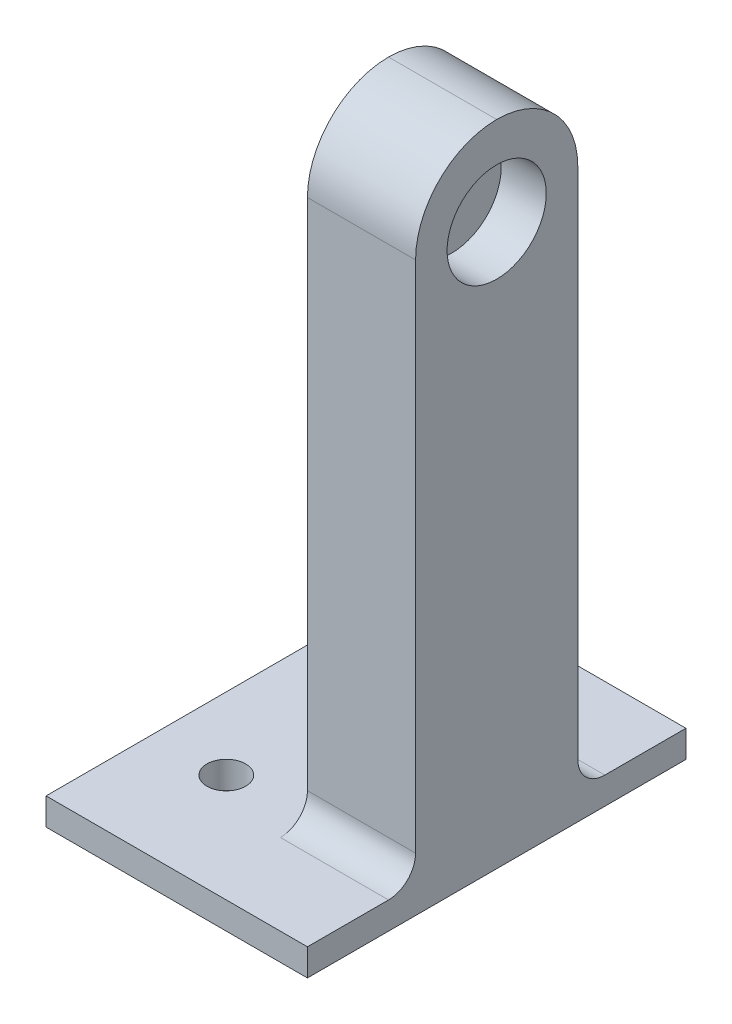
SolidWorks part; units mm, degrees
ref_plane "Front Plane" through (0, 0, 0) normal (0, 0, 1) x (1, 0, 0)
ref_plane "Top Plane" through (0, 0, 0) normal (0, 1, 0) x (1, 0, 0)
ref_plane "Right Plane" through (0, 0, 0) normal (1, 0, 0) x (0, 0, -1)
sketch "Sketch1" plane through (0, 0, 0) normal (0, 1, 0) x (1, 0, 0)
  line L1 (0, 0) -> (94, 0)
  line L2 (0, 0) -> (0, -42)
  line L3 (0, -42) -> (94, -42)
  line L4 (94, 0) -> (94, -42)
  dimension "D1" = 94
  dimension "D2" = 42
extrude "Boss-Extrude1" add sketch "Sketch1" along normal blind 3
sketch "Sketch2" plane through (0, 0, 0) normal (0, -1, 0) x (1, 0, 0)
  line L0 (94, 0) -> (0, 0) construction
  line L1 (0, 42) -> (4, 42)
  line L2 (0, 42) -> (0, 0)
  line L3 (0, 0) -> (4, 0)
  line L4 (4, 42) -> (4, 0)
  line L6 (94, 42) -> (90, 42)
  line L7 (94, 42) -> (94, 0)
  line L8 (94, 0) -> (90, 0)
  line L9 (90, 42) -> (90, 0)
  dimension "D1" = 4
  dimension "D2" = 4
extrude "Boss-Extrude2" add sketch "Sketch2" against normal blind 47
sketch "Sketch3" plane through (94, 0, 0) normal (1, 0, 0) x (0, 0, -1)
  circle B0 centre (-21, 26) radius 12.5
  circle B1 centre (-36.5, 41.5) radius 1.6
  circle B2 centre (-5.5, 41.5) radius 1.6
  circle B3 centre (-36.5, 10.5) radius 1.6
  circle B4 centre (-5.5, 10.5) radius 1.6
sketch_block_instance "stepper mounting hole pattern-1"
sketch_block "stepper mounting hole pattern" parameters "D1"=25, "D2"=3.2, "D3"=3.2, "D4"=3.2, "D5"=3.2
extrude "Cut-Extrude1" cut sketch "Sketch3" against normal through all
sketch "Sketch4" plane through (94, 0, 0) normal (1, 0, 0) x (0, 0, -1)
  line L0 (0, 47) -> (0, 0) construction
  line L1 (-42, 0) -> (0, 0)
  line L2 (-42, 0) -> (-42, 5)
  line L3 (-42, 5) -> (0, 5)
  line L4 (0, 0) -> (0, 5)
  dimension "D1" = 5
extrude "Boss-Extrude3" add sketch "Sketch4" along normal blind 40
sketch "Sketch5" plane through (0, 0, 0) normal (-1, 0, 0) x (0, 0, 1)
  line L0 (42, 47) -> (42, 0) construction
  line L1 (0, 0) -> (42, 0)
  line L2 (0, 0) -> (0, 5)
  line L3 (0, 5) -> (42, 5)
  line L4 (42, 0) -> (42, 5)
  dimension "D1" = 5
extrude "Boss-Extrude4" add sketch "Sketch5" along normal blind 38
sketch "Sketch7" plane through (0, 47, 0) normal (0, 1, 0) x (1, 0, 0)
  line L0 (-38, -42) -> (0, -42) construction
  line L1 (4, 0) -> (-38, 0)
  line L2 (4, 0) -> (4, -42)
  line L3 (4, -42) -> (-38, -42)
  line L4 (-38, 0) -> (-38, -42)
  line L5 (134, -42) -> (94, -42) construction
  line L6 (90, 0) -> (134, 0)
  line L7 (90, 0) -> (90, -42)
  line L8 (90, -42) -> (134, -42)
  line L9 (134, 0) -> (134, -42)
extrude "Boss-Extrude6" add sketch "Sketch7" along normal blind 5
sketch "Sketch9" plane through (0, 3, 0) normal (0, 1, 0) x (1, 0, 0)
  line L0 (4, -42) -> (90, -42) construction
  line L1 (90, 0) -> (90, -42) construction
  line L2 (90, 0) -> (4, 0) construction
  line L4 (4, -42) -> (4, 0) construction
  circle A0 centre (83, -20) radius 2.15
  circle A1 centre (65, -20) radius 2.15
  circle A2 centre (74, -11) radius 2.15
  circle A3 centre (74, -29) radius 2.15
  circle A4 centre (16, -12) radius 2.15
  circle A5 centre (16, -30) radius 2.15
  circle A6 centre (32, -12) radius 2.15
  circle A7 centre (32, -30) radius 2.15
  dimension "D1" = 4.3
  dimension "D2" = 22
  dimension "D3" = 7
  dimension "D4" = 18
  dimension "D5" = 9
  dimension "D6" = 18
  dimension "D7" = 9
  dimension "D8" = 18
  dimension "D9" = 12
  dimension "D10" = 12
  dimension "D11" = 16
extrude "Cut-Extrude2" cut sketch "Sketch9" against normal through all
sketch "Sketch11" plane through (0, 52, 0) normal (0, 1, 0) x (1, 0, 0)
  line L0 (4, -42) -> (4, 0) construction
  line L1 (-13, -12) -> (-3, -12)
  line L2 (-13, -12) -> (-13, -30)
  line L3 (-13, -30) -> (-3, -30)
  line L4 (-3, -12) -> (-3, -30)
  line L5 (4, 0) -> (-38, 0) construction
  line L7 (102, -12) -> (112, -12)
  line L8 (102, -12) -> (102, -30)
  line L9 (102, -30) -> (112, -30)
  line L10 (112, -12) -> (112, -30)
  line L11 (90, 0) -> (90, -42) construction
  dimension "D1" = 10
  dimension "D2" = 7
  dimension "D3" = 18
  dimension "D4" = 12
  dimension "D5" = 18
  dimension "D6" = 10
  dimension "D7" = 12
extrude "Boss-Extrude7" add sketch "Sketch11" along normal blind 20
sketch "Sketch13" plane through (-13, 0, 0) normal (-1, 0, 0) x (0, 0, 1)
  line L0 (0, 0) -> (42, 0) construction
  line L1 (12, 72) -> (12, 52) construction
  circle A0 centre (21, 62.15) radius 5.5
  dimension "D2" = 11
  dimension "D1" = 62.15
  dimension "D3" = 9
extrude "Cut-Extrude3" cut sketch "Sketch13" against normal through all
sketch "Sketch20" plane through (0, 0, 42) normal (0, 0, 1) x (1, 0, 0)
  line L0 (134, 0) -> (134, 52)
  line L1 (134, 52) -> (90, 52)
  line L2 (90, 52) -> (90, 0)
  line L3 (-38, 0) -> (134, 0) construction
  line L4 (90, 0) -> (95, 0)
  line L5 (95, 0) -> (95, 20)
  line L6 (95, 20) -> (102, 26)
  line L7 (102, 26) -> (112, 26)
  line L8 (112, 26) -> (129, 20)
  line L9 (129, 20) -> (129, 0)
  line L10 (129, 0) -> (134, 0)
  dimension "D1" = 5
  dimension "D2" = 5
  dimension "D3" = 10
  dimension "D4" = 7
  dimension "D5" = 20
  dimension "D6" = 6
extrude "Boss-Extrude11" add sketch "Sketch20" along normal blind 5
sketch "Sketch23" plane through (0, 0, 47) normal (0, 0, 1) x (1, 0, 0)
  line L0 (134, 52) -> (90, 52) construction
  line L1 (102, 52) -> (112, 52)
  line L2 (102, 52) -> (102, 26)
  line L3 (102, 26) -> (112, 26)
  line L4 (112, 52) -> (112, 26)
  line L5 (102, 52) -> (112, 52) construction
extrude "Boss-Extrude12" add sketch "Sketch23" along normal blind 50
sketch "Sketch24" plane through (112, 0, 0) normal (1, 0, 0) x (0, 0, -1)
  line L0 (-47, 26) -> (-97, 39)
  line L1 (-97, 26) -> (-97, 52) construction
  line L2 (-97, 39) -> (-97, 26)
  line L3 (-97, 26) -> (-47, 26)
extrude "Cut-Extrude7" cut sketch "Sketch24" against normal through all
sketch "Sketch25" plane through (0, 52, 0) normal (0, 1, 0) x (1, 0, 0)
  line L0 (102, -97) -> (102, -47) construction
  line L1 (102, -62) -> (112, -62)
  line L2 (102, -62) -> (102, -80)
  line L3 (102, -80) -> (112, -80)
  line L4 (112, -62) -> (112, -80)
  line L5 (112, -97) -> (112, -47) construction
  line L6 (102, -30) -> (112, -30) construction
  dimension "D1" = 18
  dimension "D2" = 32
extrude "Boss-Extrude13" add sketch "Sketch25" along normal blind 20
sketch "Sketch26" plane through (112, 0, 0) normal (1, 0, 0) x (0, 0, -1)
  line L0 (-80, 72) -> (-80, 52) construction
  line L1 (-47, 0) -> (0, 0) construction
  circle A0 centre (-71, 62.15) radius 5.5
  dimension "D1" = 11
  dimension "D2" = 9
  dimension "D3" = 62.15
extrude "Cut-Extrude8" cut sketch "Sketch26" against normal through all
sketch "Sketch27" plane through (0, 3, 0) normal (0, 1, 0) x (1, 0, 0)
  line L0 (90, 0) -> (90, -42) construction
  line L1 (41, -12) -> (53, -12)
  line L2 (41, -12) -> (41, -30)
  line L3 (41, -30) -> (53, -30)
  line L4 (53, -12) -> (53, -30)
  line L5 (4, -42) -> (90, -42) construction
  dimension "D1" = 37
  dimension "D2" = 18
  dimension "D3" = 12
  dimension "D4" = 12
extrude "Boss-Extrude14" add sketch "Sketch27" along normal blind 69
sketch "Sketch28" plane through (53, 0, 0) normal (1, 0, 0) x (0, 0, -1)
  line L0 (-12, 72) -> (-12, 3) construction
  line L1 (-47, 0) -> (0, 0) construction
  circle A0 centre (-21, 62.15) radius 5.5
  dimension "D1" = 11
  dimension "D2" = 9
  dimension "D3" = 62.15
extrude "Cut-Extrude10" cut sketch "Sketch28" against normal blind 5
sketch "Sketch29" plane through (41, 0, 0) normal (-1, 0, 0) x (0, 0, 1)
  line L0 (30, 72) -> (30, 3) construction
  line L2 (0, 0) -> (42, 0) construction
  circle A0 centre (21, 62.15) radius 5.5
  dimension "D2" = 11
  dimension "D1" = 9
  dimension "D3" = 62.15
extrude "Cut-Extrude11" cut sketch "Sketch29" against normal blind 5
fillet "Fillet4" radius 9 8 edges at (-8, 72, 12) (-8, 72, 30) (107, 72, 12) (107, 72, 30) (107, 72, 62) (107, 72, 80) (47, 72, 12) (47, 72, 30)
fillet "Fillet3" radius 3 14 edges at (-8, 52, 12) (-8, 52, 30) (107, 52, 12) (107, 52, 30) (107, 52, 62) (107, 52, 80) (129, 20, 44.5) (112, 26, 44.5) (102, 26, 44.5) (95, 20, 44.5) (107, 52, 97) (107, 39, 97) (47, 3, 12) (47, 3, 30)
sketch "Sketch30" plane through (0, 0, 0) normal (0, -1, 0) x (1, 0, 0)
  line L0 (-38, 42) -> (90, 42) construction
  line L1 (-38, 0) -> (22, 0)
  line L2 (-38, 0) -> (-38, 42)
  line L3 (-38, 42) -> (22, 42)
  line L4 (22, 0) -> (22, 42)
  line L6 (53, 100) -> (134, 100)
  line L7 (53, 100) -> (53, 0)
  line L8 (53, 0) -> (134, 0)
  line L9 (134, 100) -> (134, 0)
  dimension "D1" = 60
  dimension "D2" = 100
extrude "Cut-Extrude12" cut sketch "Sketch30" against normal through all
sketch "Sketch31" plane through (0, 3, 0) normal (0, 1, 0) x (1, 0, 0)
  line L0 (22, -42) -> (53, -42) construction
  line L1 (22, 0) -> (24, 0)
  line L2 (22, 0) -> (22, -42)
  line L3 (22, -42) -> (24, -42)
  line L4 (24, 0) -> (24, -42)
  dimension "D1" = 2
extrude "Cut-Extrude13" cut sketch "Sketch31" against normal blind 10
